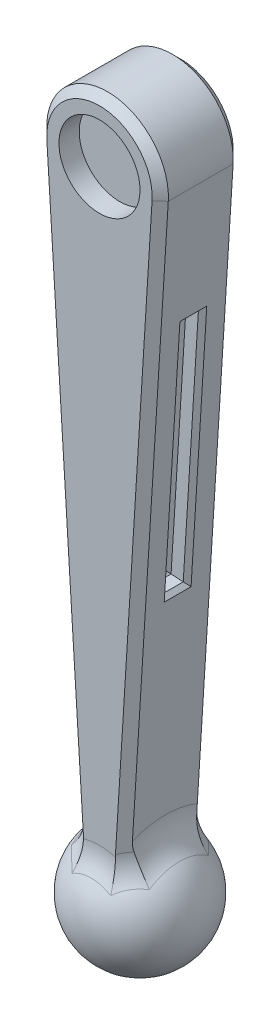
SolidWorks part; units mm, degrees
ref_plane "Front Plane" through (0, 0, 0) normal (0, 0, 1) x (1, 0, 0)
ref_plane "Top Plane" through (0, 0, 0) normal (0, 1, 0) x (1, 0, 0)
ref_plane "Right Plane" through (0, 0, 0) normal (1, 0, 0) x (0, 0, -1)
sketch "Sketch1" plane through (0, 0, 0) normal (0, 0, 1) x (1, 0, 0)
  line L0 (0, 0) -> (0, -160) construction
  line L1 (-14.9707, -0.9375) -> (-4.9902, -160.3125)
  line L2 (14.9707, -0.9375) -> (4.9902, -160.3125)
  arc A0 (14.9707, -0.9375) -> (-14.9707, -0.9375) centre (0, 0) ccw
  arc A1 (-4.9902, -160.3125) -> (4.9902, -160.3125) centre (0, -160) ccw
  dimension "D1" = 30
  dimension "D3" = 10
  dimension "D2" = 160
extrude "Boss-Extrude1" add sketch "Sketch1" along normal mid plane 20
sketch "Sketch2" plane through (0, 0, 10) normal (0, 0, 1) x (1, 0, 0)
  circle A0 centre (0, 0) radius 10
  arc A1 (14.9707, -0.9375) -> (-14.9707, -0.9375) centre (0, 0) ccw construction
  dimension "D1" = 5
extrude "Cut-Extrude1" cut sketch "Sketch2" against normal blind 5
mirror "Mirror1" about plane through (0, 0, 0) normal (0, 0, 1) of "Cut-Extrude1"
sketch "Sketch4" plane through (0, 0, 0) normal (0, 0, 1) x (1, 0, 0)
  line L0 (0, -145) -> (0, -175) construction
  line L1 (0, -145) -> (0, -175)
  arc A0 (0, -145) -> (0, -175) centre (0, -160) ccw
  dimension "D1" = 30
revolve "Revolve1" add sketch "Sketch4" angle 360 about L0
chamfer "Chamfer1" distance 2 angle 45 6 edges at (-10.2929, -75.6348, -10) (0, 15, -10) (10.2929, -75.6348, -10) (-10.2929, -75.6348, 10) (0, 15, 10) (10.2929, -75.6348, 10)
fillet "Fillet1" radius 10 8 edges at (4.679, -148.9659, -9.0198) (0, -148.8197, -10) (-4.679, -148.9659, -9.0198) (-5.8741, -146.198, 0) (-4.679, -148.9659, 9.0198) (0, -148.8197, 10) (4.679, -148.9659, 9.0198) (5.8741, -146.198, 0)
sketch "Sketch5" plane through (14.9707, -0.9375, 0) normal (0.998, -0.0625, 0) x (0, 0, -1)
  line L0 (0, 0) -> (0, -90) construction
  line L1 (-2.3123, -30) -> (2.3123, -30)
  line L2 (-2.3123, -30) -> (-2.3123, -90)
  line L3 (-2.3123, -90) -> (2.3123, -90)
  line L4 (2.3123, -30) -> (2.3123, -90)
  line L5 (-8, 0) -> (8, 0) construction
  dimension "D1" = 60
  dimension "D2" = 30
extrude "Cut-Extrude2" cut sketch "Sketch5" against normal blind 5
chamfer "Chamfer2" distance 1 angle 45 8 edges at (8.1054, -30.5663, 0) (6.2304, -60.5077, -2.3123) (4.3554, -90.449, 0) (6.2304, -60.5077, 2.3123) (11.2207, -60.8202, 2.3123) (9.3457, -90.7615, 0) (11.2207, -60.8202, -2.3123) (13.0957, -30.8788, 0)
sketch "Sketch6" plane through (0, 0, 0) normal (0, 0, 1) x (1, 0, 0)
  line L0 (0, 15) -> (0, -175) construction
  arc A0 (14.9707, -0.9375) -> (-14.9707, -0.9375) centre (0, 0) ccw construction
  arc A1 (-9.7324, -148.586) -> (9.7324, -148.586) centre (0, -160) ccw construction
  point P8 (0, -80)
sketch "Sketch7" plane through (0, 0, 0) normal (0, 0, 1) x (1, 0, 0)
  line L0 (0, 15) -> (0, -175) construction
  arc A0 (-9.7324, -148.586) -> (9.7324, -148.586) centre (0, -160) ccw construction
  point P0 (0, -160)
  point P1 (0, 0)
